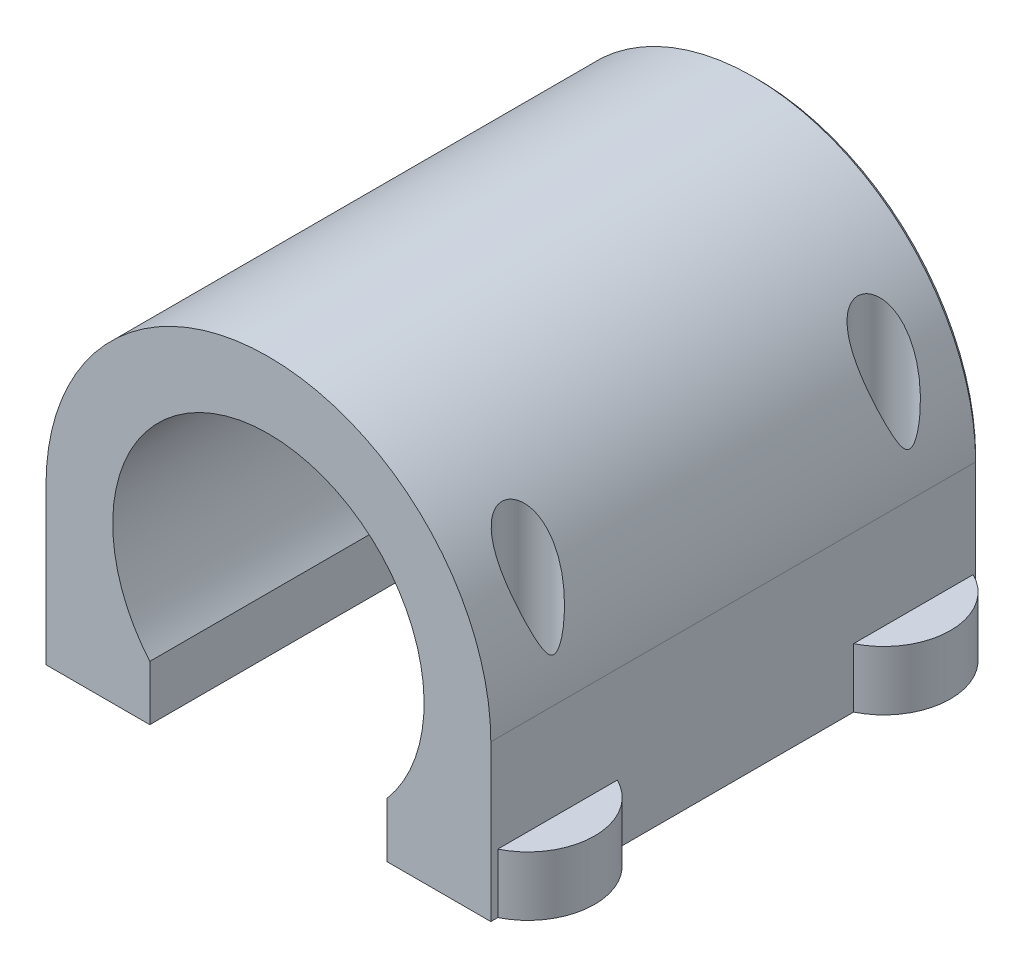
SolidWorks part; units mm, degrees
material "Custom Plastic"
ref_plane "Front Plane" through (0, 0, 0) normal (0, 0, 1) x (1, 0, 0)
ref_plane "Top Plane" through (0, 0, 0) normal (0, 1, 0) x (1, 0, 0)
ref_plane "Right Plane" through (0, 0, 0) normal (1, 0, 0) x (0, 0, -1)
sketch "Sketch1" plane through (0, 0, 0) normal (0, 0, 1) x (1, 0, 0)
  line L0 (-23.622, -10.5) -> (30.4823, -10.5) construction
  line L1 (-23.622, -16.5) -> (30.4823, -16.5) construction
  line L2 (8, -6.8007) -> (8, -10.5)
  line L3 (8, -10.5) -> (15, -10.5)
  line L4 (-15, -10.5) -> (-8, -10.5)
  line L5 (-8, -6.8007) -> (-8, -10.5)
  line L6 (15, 0) -> (15, -10.5)
  line L12 (-15, -10.5) -> (-15, 0)
  arc A4 (8, -6.8007) -> (-8, -6.8007) centre (0, 0) ccw
  arc A5 (15, 0) -> (-15, 0) centre (0, 0) ccw
  dimension "D1" = 16
  dimension "D6" = 21
  dimension "D7" = 4.5
  dimension "D2" = 6
extrude "Boss-Extrude1" add sketch "Sketch1" along normal blind 33
sketch "Sketch4" plane through (0, -10.5, 0) normal (0, -1, 0) x (1, 0, 0)
  line L0 (13, 28.5) -> (15, 28.5) construction
  line L2 (15, 33) -> (15, 0) construction
  line L3 (15, 16.5) -> (-15, 16.5) construction
  line L4 (-15, 33) -> (-15, 0) construction
  circle A0 centre (13, 28.5) radius 4.5
  dimension "D1" = 9
  dimension "D2" = 2
  dimension "D3" = 12
extrude "Boss-Extrude2" add sketch "Sketch4" against normal blind 4
sketch "Sketch2" plane through (0, -10.5, 0) normal (0, -1, 0) x (1, 0, 0)
  line L0 (13, 57) -> (13, 0) construction
  circle A0 centre (13, 28.5) radius 1.75
  arc A1 (15, 24.4689) -> (15, 32.5311) centre (13, 28.5) ccw construction
  dimension "D1" = 3.5
extrude "Cut-Extrude1" cut sketch "Sketch2" against normal blind 30
chamfer "Chamfer1" distance 0.3 angle 45 8 edges at (-15, -5.25, 0) (-11.5, -10.5, 0) (-8, -8.6504, 0) (0, 10.5, 0) (8, -8.6504, 0) (11.5, -10.5, 0) (15, -5.25, 0) (0, 15, 0)
ref_plane "Plane1" through (0, 0, 16.5) normal (0, 0, 1) x (1, 0, 0)
mirror "Mirror3" about plane through (0, 0, 16.5) normal (0, 0, 1) of "Cut-Extrude1", "Boss-Extrude2"
mirror "Mirror4" about plane through (0, 0, 0) normal (1, 0, 0) of "Mirror3", "Cut-Extrude1", "Boss-Extrude2"
